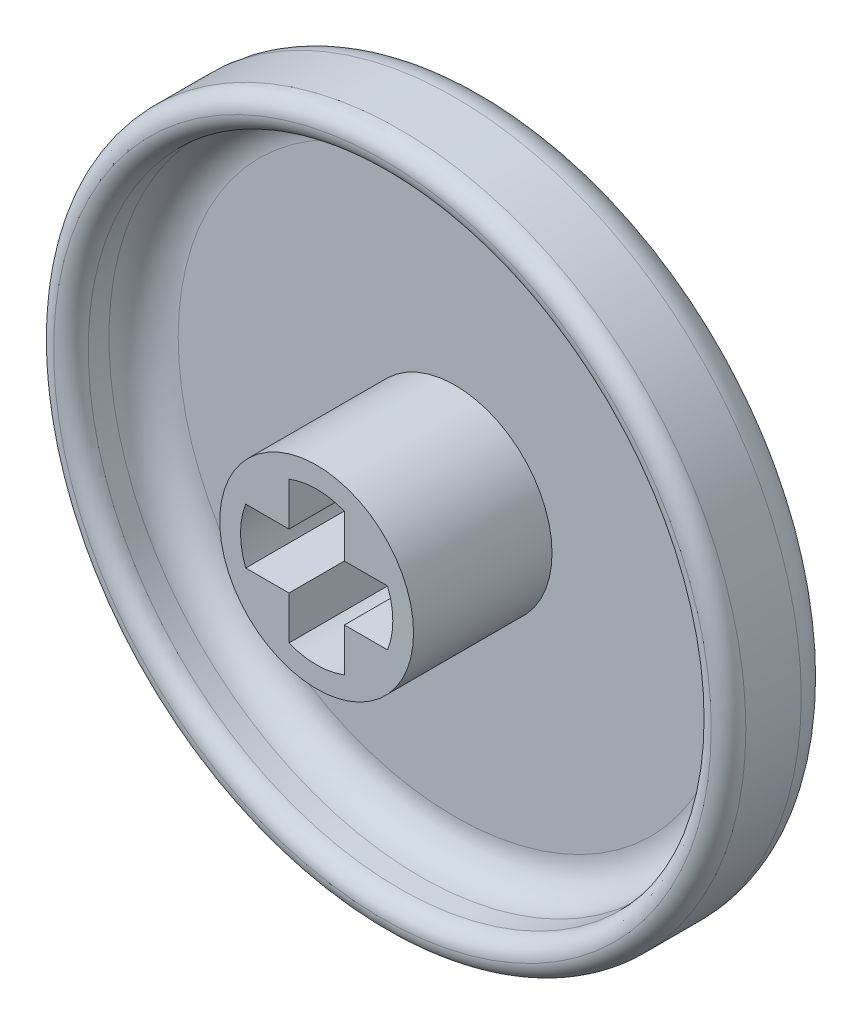
SolidWorks part; units mm, degrees
ref_plane "前视基准面" through (0, 0, 0) normal (0, 0, 1) x (1, 0, 0)
ref_plane "上视基准面" through (0, 0, 0) normal (0, 1, 0) x (1, 0, 0)
ref_plane "右视基准面" through (0, 0, 0) normal (1, 0, 0) x (0, 0, -1)
other "Configuration Table"
sketch "草图1" plane through (0, 0, 0) normal (0, 0, 1) x (1, 0, 0)
  line L0 (-0.8, 0) -> (0.8, 0) construction
  line L1 (0, -0.8) -> (0, 0.8) construction
  line L55 (-2.0494, 0.8) -> (-0.8, 0.8)
  line L56 (-2.0494, -0.8) -> (-0.8, -0.8)
  line L61 (0.8, -2.0494) -> (0.8, -0.8)
  line L62 (-0.8, -2.0494) -> (-0.8, -0.8)
  line L102 (-0.8, 0.8) -> (-0.8, 2.0494)
  line L103 (0.8, -0.8) -> (2.0494, -0.8)
  line L104 (0.8, 0.8) -> (2.0494, 0.8)
  line L105 (0.8, 0.8) -> (0.8, 2.0494)
  circle A5 centre (0, 0) radius 10
  circle A7 centre (0, 0) radius 9
  circle A9 centre (0, 0) radius 2.8
  circle A10 centre (0, 0) radius 2.2
  point P5 (0, 0)
  point P6 (0, 0)
  point P7 (0, 0)
  point P8 (0, 0)
  point P10 (0, 0)
  point P12 (0, 0)
  point P17 (0, 0.8)
  point P20 (0, -0.8)
  point P24 (0.8, 0)
  point P29 (-0.8, 0)
  dimension "D1" = 5.6
  dimension "D7" = 20
  dimension "D4" = 4.4
  dimension "D3" = 1.6
  dimension "D2" = 1.6
  dimension "D9" = 1
extrude "凸台-拉伸1" add sketch "草图1" along normal blind 4 contours L56 A10 L62 | L102 A10 L55 | L61 A10 L103 | L104 A10 L105 | A9 A10 region at (-1.2738, 1.2738, 0) region at (-1.2738, -1.2738, 0) region at (1.2738, 1.2738, 0) region at (1.2738, -1.2738, 0) region at (-2.7208, 0, 0)
extrude "凸台-拉伸2" add sketch "草图1<27>" against normal blind 1 contours L104 A10 L105 | L102 A10 L55 | L61 A10 L103 | L56 A10 L62 | L105 A10 L102 L55 L56 L62 L61 L103 L104 | A9 A10 | A7 A9 region at (-1.2738, 1.2738, 0) region at (0, 0, 0) region at (-1.2738, -1.2738, 0) region at (1.2738, 1.2738, 0) region at (1.2738, -1.2738, 0) region at (-8.7454, 0, 0) region at (-2.7208, 0, 0)
sketch "草图1<27>" plane through (0, 0, 0) normal (0, 0, 1) x (1, 0, 0) same geometry as "草图1"
extrude "凸台-拉伸3" add sketch "草图1<28>" along normal blind 2.1 and the other way blind 1 contours A5 A7 region at (-9.7172, 0, 0)
sketch "草图1<28>" plane through (0, 0, 0) normal (0, 0, 1) x (1, 0, 0) same geometry as "草图1"
fillet "圆角1" radius 1 2 edges at (10, 0, -1) (9, 0, 0)
fillet "圆角2" radius 0.5 1 edges at (9, 0, 2.1) type face fillet first side face at (9, 0, 1) second side face at (9, 0, 2.1)
fillet "圆角3" radius 0.5 1 edges at (10, 0, 2.1) type face fillet first side face at (9.5, 0, 2.1) second side face at (10, 0, 0)
